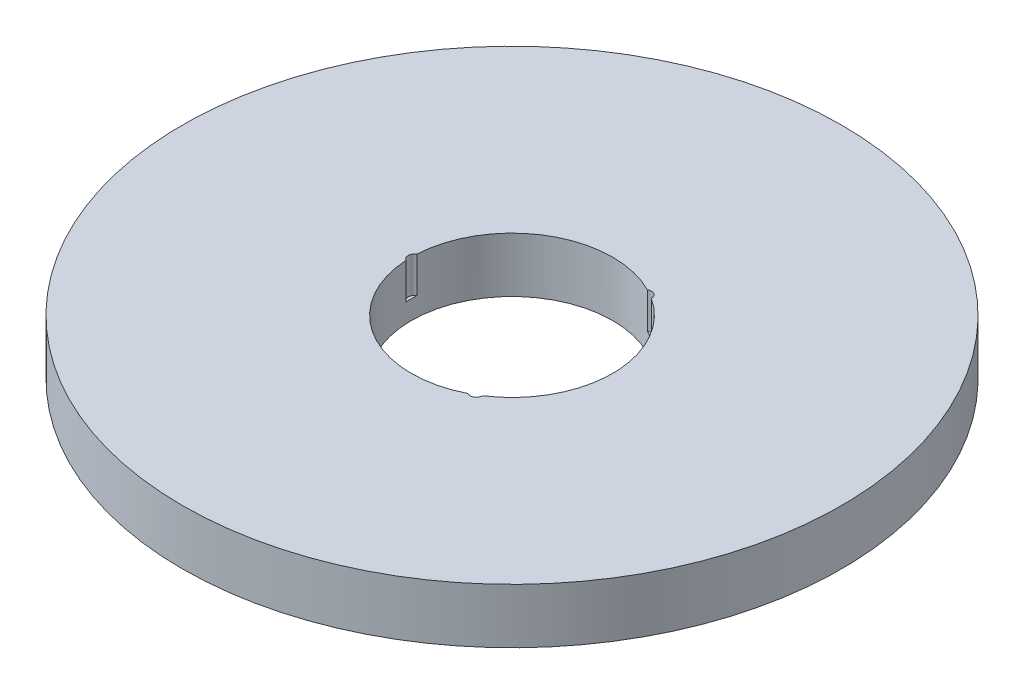
SolidWorks part; units mm, degrees
ref_plane "Front Plane" through (0, 0, 0) normal (0, 0, 1) x (1, 0, 0)
ref_plane "Top Plane" through (0, 0, 0) normal (0, 1, 0) x (1, 0, 0)
ref_plane "Right Plane" through (0, 0, 0) normal (1, 0, 0) x (0, 0, -1)
sketch "Sketch1" plane through (0, 0, 0) normal (0, 1, 0) x (1, 0, 0)
  circle A0 centre (0, 0) radius 90
  dimension "FLANGE_OD" = 180
extrude "Boss-Extrude1" add sketch "Sketch1" along normal blind 15
sketch "Sketch2" plane through (0, 0, 0) normal (0, 1, 0) x (1, 0, 0)
  circle A0 centre (0, 0) radius 27.5
  dimension "BORE_D" = 55
extrude "Cut-Extrude1" cut sketch "Sketch2" along normal through all
sketch "Sketch3" plane through (0, 15, 0) normal (0, 1, 0) x (1, 0, 0)
  circle A0 centre (0, 0) radius 26.6134 construction
  circle A1 centre (-26.6134, 0) radius 1.7114
  dimension "BOLT_D" = 3.4228
  dimension "BOLT_PCD" = 53.2268
extrude "Cut-Extrude2" cut sketch "Sketch3" against normal blind 9.8285
pattern_circular "CirPattern1" count 3 over 360 about axis through (0, 0, 0) along (0, 1, 0) of "Cut-Extrude2"
